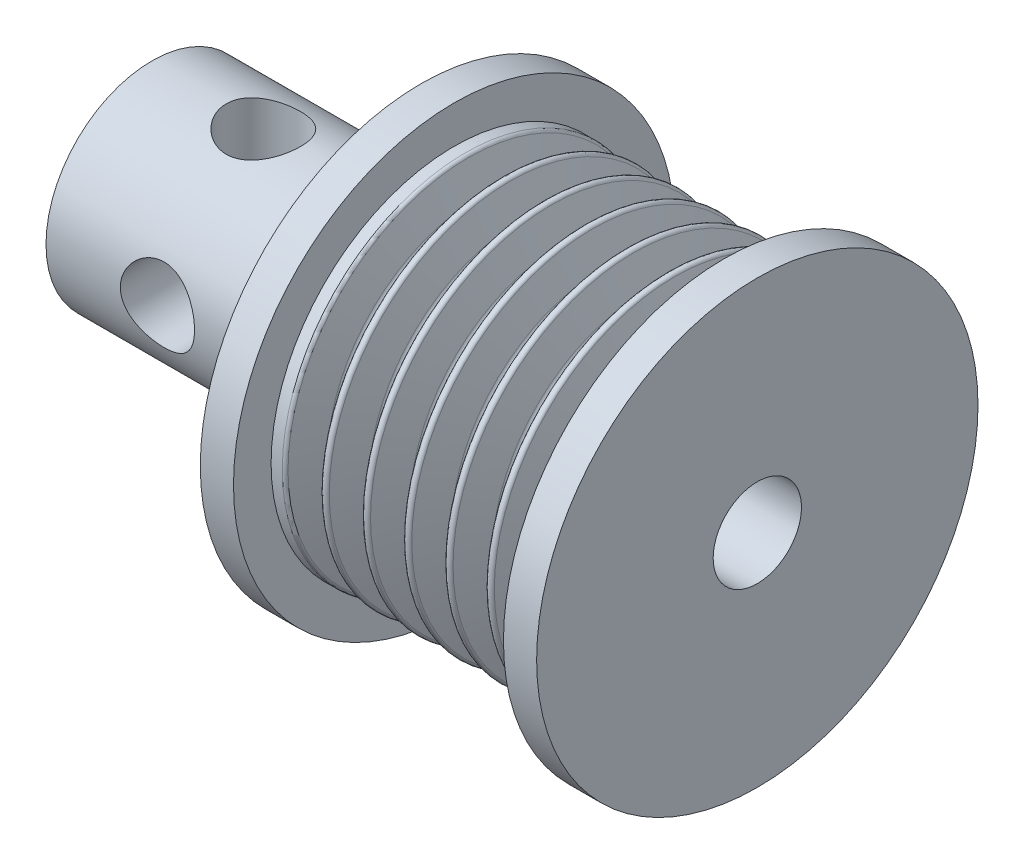
SolidWorks part; units mm, degrees
material "AISI 4130 Steel, annealed at 865C"
ref_plane "Front Plane" through (0, 0, 0) normal (0, 0, 1) x (1, 0, 0)
ref_plane "Top Plane" through (0, 0, 0) normal (0, 1, 0) x (1, 0, 0)
ref_plane "Right Plane" through (0, 0, 0) normal (1, 0, 0) x (0, 0, -1)
sketch "Sketch1" plane through (0, 0, 0) normal (0, 0, 1) x (1, 0, 0)
  line L0 (0, 0) -> (0, 2.5) construction
  line L1 (0, 2.5) -> (34.29, 2.5)
  line L2 (34.29, 2.5) -> (34.29, 12.5)
  line L3 (34.29, 12.5) -> (15.24, 12.5)
  line L4 (15.24, 12.5) -> (15.24, 6)
  line L5 (0, 0) -> (13.5959, 0) construction
  line L8 (15.24, 6) -> (0, 6)
  line L9 (0, 6) -> (0, 2.5)
  dimension "D1" = 25
  dimension "D3" = 19.05
  dimension "D6" = 12
  dimension "D7" = 15.24
revolve "Revolve1" add sketch "Sketch1" angle 360 about L5
sketch "Sketch2" plane through (0, 0, 0) normal (0, 0, 1) x (1, 0, 0)
  line L0 (29.4386, 12.5) -> (29.4386, 10.3699)
  line L1 (15.24, 6) -> (15.24, -6) construction
  line L2 (29.6295, 10.2362) -> (30.2251, 8.5999)
  line L3 (30.9889, 8.5999) -> (31.5845, 10.2362)
  line L4 (31.7754, 10.3699) -> (31.7754, 12.5)
  line L5 (31.7754, 12.5) -> (29.4386, 12.5)
  line L6 (29.4386, 11.43) -> (31.7754, 11.43) construction
  line L7 (15.24, 0) -> (34.29, 0) construction
  line L8 (29.6295, 10.2362) -> (31.5845, 10.2362) construction
  line L9 (29.4386, 12.5) -> (27.1018, 12.5) construction
  line L10 (34.29, 12.5) -> (15.24, 12.5) construction
  line L11 (27.1018, 12.5) -> (24.765, 12.5) construction
  line L13 (24.765, 0) -> (24.765, 12.5) construction
  line L15 (34.29, -12.5) -> (34.29, 12.5) construction
  arc A0 (29.4386, 10.3699) -> (29.6295, 10.2362) centre (29.4386, 10.1667) cw
  arc A1 (30.2251, 8.5999) -> (30.9889, 8.5999) centre (30.607, 8.7389) ccw
  arc A2 (31.5845, 10.2362) -> (31.7754, 10.3699) centre (31.7754, 10.1667) cw
  dimension "D5" = 0.2032
  dimension "D2" = 2.3368
  dimension "D4" = 1.1938
  dimension "D6" = 40
  dimension "D7" = 11.43
revolve "Cut-Revolve1" cut sketch "Sketch2" angle 360 about L7
pattern_linear "LPattern1" count 6 spacing 2.3368 along (-1, 0, 0) of "Cut-Revolve1"
sketch "Sketch3" plane through (0, 0, 0) normal (0, 0, 1) x (1, 0, 0)
  line L0 (31.7754, 12.5) -> (32.4104, 12.5)
  line L1 (34.29, 12.5) -> (31.7754, 12.5) construction
  line L2 (32.4104, 12.5) -> (32.4104, 10.3699)
  line L3 (32.4104, 10.3699) -> (31.7754, 10.3699)
  line L4 (31.7754, 12.5) -> (31.7754, -12.5) construction
  line L5 (31.7754, 10.3699) -> (31.7754, 12.5)
  line L6 (31.7754, 10.3699) -> (31.7754, -10.3699) construction
  line L7 (30.607, 8.3325) -> (30.607, 11.4458) construction
  line L8 (24.765, 10.3699) -> (24.765, 14.7012) construction
  line L9 (17.7546, 10.3699) -> (17.7546, 12.5)
  line L10 (17.1196, 10.3699) -> (17.7546, 10.3699)
  line L11 (17.1196, 12.5) -> (17.1196, 10.3699)
  line L12 (17.7546, 12.5) -> (17.1196, 12.5)
  line L13 (0, 0) -> (26.9583, 0) construction
  arc A0 (30.2251, 8.5999) -> (30.9889, 8.5999) centre (30.607, 8.7389) ccw construction
  arc A1 (24.9559, 10.2362) -> (24.5741, 10.2362) centre (24.765, 10.1667) ccw construction
  dimension "D1" = 1.8034
revolve "Cut-Revolve2" cut sketch "Sketch3" angle 360 about L13
fillet "Fillet1" radius 0.762 1 edges at (15.24, 0, 6)
ref_plane "Plane1" through (0, 6, 0) normal (0, 1, 0) x (1, 0, 0)
hole_wizard "M5x0.8 Tapped Hole1" positions "Sketch6" profile "Sketch5" tap size "M5x0.8" standard "ANSI Metric" end condition up to next
sketch "Sketch6" plane through (0, 6, 0) normal (0, 1, 0) x (1, 0, 0)
  line L1 (6.311, 0) -> (0, 0) construction
  line L7 (9.74, 6) -> (9.74, -6) construction
  line L8 (14.478, 6) -> (0, 6) construction
  line L9 (0, -6) -> (14.478, -6) construction
  line L11 (15.24, 6.762) -> (15.24, -6.762) construction
  circle A0 centre (6.311, 0) radius 3.429 construction
  point P0 (6.311, 0)
  dimension "D1" = 6.858
  dimension "D2" = 5.5
sketch "Sketch5" plane through (6.311, 6, 0) normal (1, 0, 0) x (0, 0, 1)
  line L0 (0, 0) -> (0, 3.5)
  line L1 (0, 3.5) -> (2.1, 3.5)
  line L2 (2.1, 3.5) -> (2.1, 0)
  line L5 (2.1, 0) -> (0, 0)
  line L11 (0, -6.35) -> (0, 107.95) construction
  dimension "Thru Tap Drill Dia." = 4.2
  dimension "Thru Tap Drill Depth" = 3.5
pattern_circular "CirPattern1" count 2 over 90 about axis through (0, 0, 0) along (-1, 0, 0) of "M5x0.8 Tapped Hole1" reverse direction yes
equation "\"D2@Sketch1\"=5mm"
equation "\"D4@Sketch2\"=0.094in/2"
equation "\"D1@Sketch1\"=25mm"
equation "\"D3@Sketch1\"=0.75in"
equation "\"D7@Sketch2\"=0.9in/2"
equation "\"D7@Sketch1\"=0.60in"
equation "\"D2@Sketch6\"=5.5mm"
equation "\"D6@Sketch1\"=12mm"
